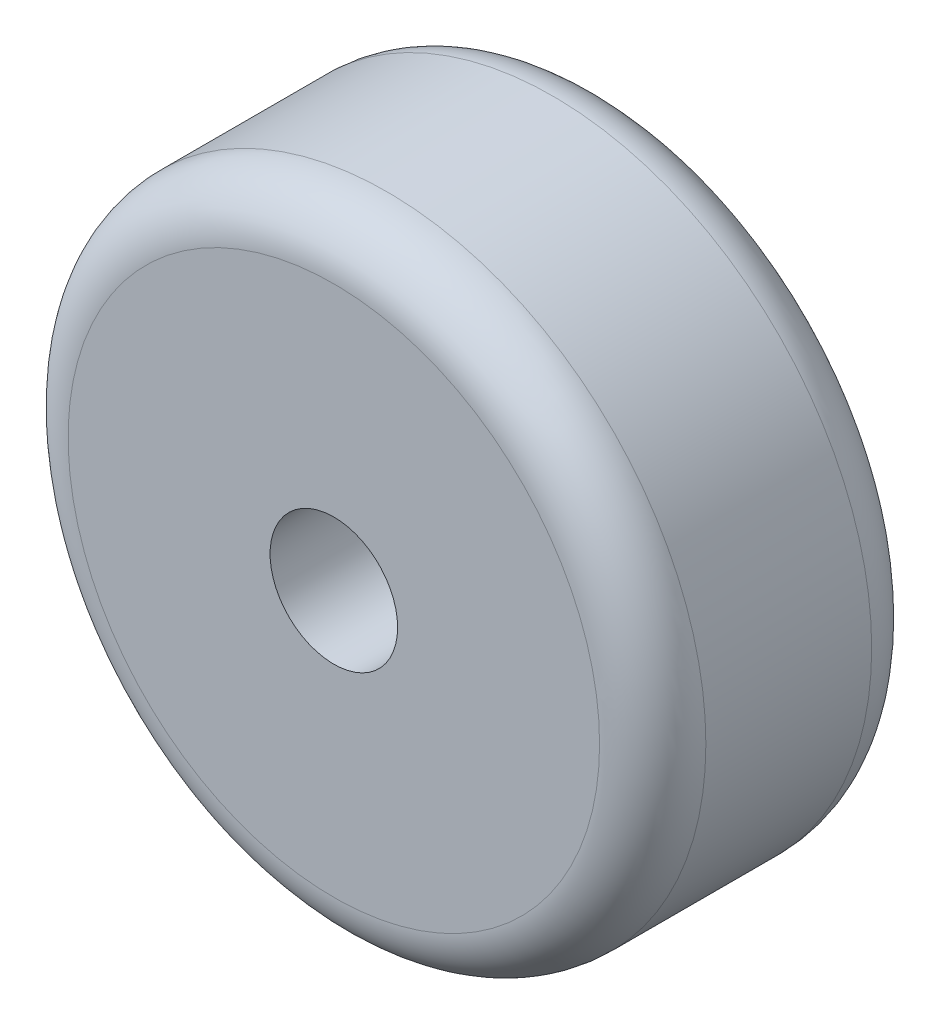
SolidWorks part; units mm, degrees
ref_plane "正面" through (0, 0, 0) normal (0, 0, 1) x (1, 0, 0)
ref_plane "平面" through (0, 0, 0) normal (0, 1, 0) x (1, 0, 0)
ref_plane "右側面" through (0, 0, 0) normal (1, 0, 0) x (0, 0, -1)
sketch "ｽｹｯﾁ1" plane through (0, 0, 0) normal (0, 0, 1) x (1, 0, 0)
  circle A0 centre (0, 0) radius 30
  circle A1 centre (0, 0) radius 6
  dimension "D1" = 60
  dimension "D2" = 12
extrude "ﾎﾞｽ - 押し出し1" add sketch "ｽｹｯﾁ1" along normal blind 25.6
fillet "ﾌｨﾚｯﾄ2" radius 5 2 edges at (30, 0, 25.6) (30, 0, 0)
